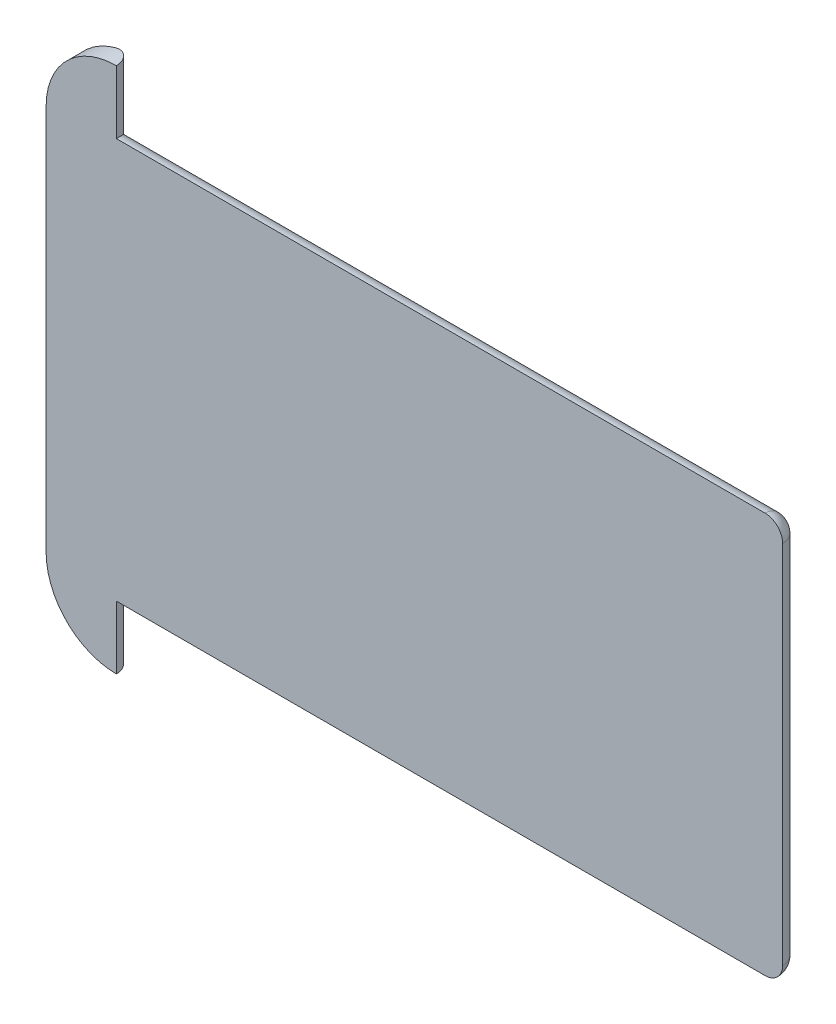
SolidWorks part; units mm, degrees
ref_plane "Front Plane" through (0, 0, 0) normal (0, 0, 1) x (1, 0, 0)
ref_plane "Top Plane" through (0, 0, 0) normal (0, 1, 0) x (1, 0, 0)
ref_plane "Right Plane" through (0, 0, 0) normal (1, 0, 0) x (0, 0, -1)
sketch "Sketch1" plane through (0, 0, 0) normal (0, 0, 1) x (1, 0, 0)
  line L0 (-108.3102, -37.6934) -> (-108.3102, -19.7138)
  line L2 (-128.3102, 92.3066) -> (-128.3102, -17.6934)
  line L4 (81.3991, 89.327) -> (81.3991, -14.7138)
  line L5 (-108.3102, -19.7138) -> (76.3991, -19.7138)
  line L6 (-128.3102, 37.3066) -> (81.3991, 37.3066) construction
  line L7 (-108.3102, 112.3066) -> (-108.3102, 94.327)
  line L8 (-108.3102, 94.327) -> (76.3991, 94.327)
  arc A0 (-128.3102, -17.6934) -> (-108.3102, -37.6934) centre (-108.3102, -17.6934) ccw
  arc A1 (-108.3102, 112.3066) -> (-128.3102, 92.3066) centre (-108.3102, 92.3066) ccw
  arc A2 (76.3991, -19.7138) -> (81.3991, -14.7138) centre (76.3991, -14.7138) ccw
  arc A3 (76.3991, 94.327) -> (81.3991, 89.327) centre (76.3991, 89.327) cw
  point P14 (81.3991, -19.7138)
  point P17 (81.3991, 94.327)
  dimension "D1" = 20
  dimension "D2" = 5
extrude "Boss-Extrude1" add sketch "Sketch1" along normal blind 5
fillet "Fillet1" radius 5 5 edges at (-15.9556, -19.7138, 0) (79.9346, -18.2493, 0) (81.3991, 37.3066, 0) (79.9346, 92.8625, 0) (-15.9556, 94.327, 0)
fillet "Fillet3" radius 5 1 edges at (-108.3102, 100.8168, 0)
fillet "Fillet4" radius 5 1 edges at (-108.3102, -26.2036, 0)
